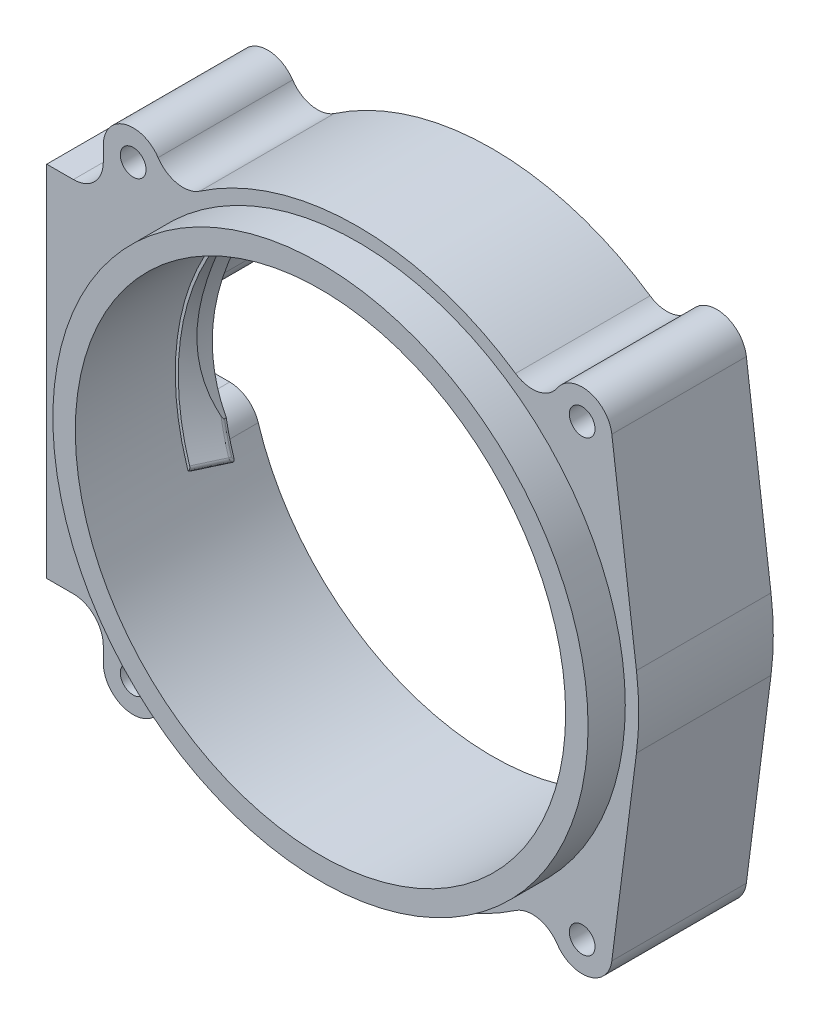
SolidWorks part; units mm, degrees
material "ABS"
ref_plane "前视基准面" through (0, 0, 0) normal (0, 0, 1) x (1, 0, 0)
ref_plane "上视基准面" through (0, 0, 0) normal (0, 1, 0) x (1, 0, 0)
ref_plane "右视基准面" through (0, 0, 0) normal (1, 0, 0) x (0, 0, -1)
sketch "草图1" plane through (0, 0, 0) normal (0, 0, 1) x (1, 0, 0)
  line L0 (0, 0) -> (50000, 0) construction
  line L1 (-52, 8.75) -> (-52, -8.75) construction
  line L2 (-52, 8.75) -> (-52, 30)
  line L3 (-52, -8.75) -> (-52, -30)
  line L4 (-52, 8.75) -> (-43.8969, 8.75)
  line L5 (-52, -8.75) -> (-43.8969, -8.75)
  line L6 (-42.54, 37.5) -> (-42.54, 35)
  line L7 (-47.54, 30) -> (-52, 30)
  line L8 (-47.54, -30) -> (-52, -30)
  line L9 (-42.54, -37.5) -> (-42.54, -35)
  line L10 (0, 0) -> (0, -50000) construction
  line L11 (42.4995, 38.1352) -> (46.6192, 5.9711)
  line L12 (42.4995, -38.1352) -> (46.6192, -5.9711)
  arc A0 (-39.1255, -12.2554) -> (-39.1255, 12.2554) centre (0, 0) ccw
  arc A1 (-40.0554, 8.75) -> (-40.0554, -8.75) centre (0, 0) ccw construction
  circle A2 centre (-37.54, 37.5) radius 2.15
  circle A3 centre (-37.54, -37.5) radius 2.15
  arc A4 (-33.3722, 40.2622) -> (-42.54, 37.5) centre (-37.54, 37.5) ccw
  arc A5 (-42.54, -37.5) -> (-33.3722, -40.2622) centre (-37.54, -37.5) ccw
  arc A6 (-26.3963, -38.8874) -> (26.3963, -38.8874) centre (0, 0) ccw
  arc A7 (-33.3722, 40.2622) -> (-26.3963, 38.8874) centre (-29.2045, 43.0244) ccw
  arc A8 (-33.3722, -40.2622) -> (-42.54, -37.5) centre (-37.54, -37.5) cw
  arc A9 (-33.3722, -40.2622) -> (-26.3963, -38.8874) centre (-29.2045, -43.0244) cw
  circle A10 centre (37.54, -37.5) radius 2.15
  circle A11 centre (37.54, 37.5) radius 2.15
  arc A12 (42.4995, 38.1352) -> (33.3722, 40.2622) centre (37.54, 37.5) ccw
  arc A13 (33.3722, -40.2622) -> (42.4995, -38.1352) centre (37.54, -37.5) ccw
  arc A14 (33.3722, 40.2622) -> (26.3963, 38.8874) centre (29.2045, 43.0244) cw
  arc A15 (33.3722, -40.2622) -> (26.3963, -38.8874) centre (29.2045, -43.0244) ccw
  arc A16 (26.3963, 38.8874) -> (-26.3963, 38.8874) centre (0, 0) ccw
  arc A17 (46.6192, -5.9711) -> (46.6192, 5.9711) centre (0, 0) ccw
  arc A18 (-47.54, -30) -> (-42.54, -35) centre (-47.54, -35) cw
  arc A19 (-42.54, 35) -> (-47.54, 30) centre (-47.54, 35) cw
  arc A20 (-43.8969, 8.75) -> (-39.1255, 12.2554) centre (-43.8969, 13.75) ccw
  arc A21 (-43.8969, -8.75) -> (-39.1255, -12.2554) centre (-43.8969, -13.75) cw
  point P8 (-52, 0)
  point P44 (-42.54, -30)
  point P47 (-42.54, 30)
  dimension "D1" = 82
  dimension "D5" = 4.3
  dimension "D6" = 75
  dimension "D8" = 10
  dimension "D9" = 94
  dimension "D10" = 5
  dimension "D11" = 10
  dimension "D12" = 5
  dimension "D13" = 5
  dimension "D14" = 5
  dimension "D15" = 5
  dimension "D2" = 17.5
  dimension "D3" = 52
  dimension "D4" = 60
  dimension "D7" = 14.46
extrude "凸台-拉伸1" add sketch "草图1" along normal blind 22.5 contours A21 L5 L3 L8 A18 L9 A5 A9 A6 A15 A13 L12 A17 L11 A12 A14 A16 A7 A4 L6 A19 L7 L2 L4 A20 A0 A10 A3 A2 A11 region at (-50.6348, 19.375, 0)
sketch "草图3" plane through (0, 0, 22.5) normal (0, 0, 1) x (1, 0, 0)
  line L0 (-52, -8.75) -> (-43.8969, -8.75) construction
  line L1 (-52, 8.75) -> (-43.8969, 8.75) construction
  line L2 (-52, -8.75) -> (-43.8969, -8.75)
  line L3 (-52, 8.75) -> (-43.8969, 8.75)
  line L4 (-52, 8.75) -> (-52, -8.75)
  arc A1 (-39.1255, -12.2554) -> (-43.8969, -8.75) centre (-43.8969, -13.75) ccw construction
  arc A2 (-43.8969, 8.75) -> (-39.1255, 12.2554) centre (-43.8969, 13.75) ccw construction
  arc A3 (-39.1255, -12.2554) -> (-43.8969, -8.75) centre (-43.8969, -13.75) ccw
  arc A4 (-43.8969, 8.75) -> (-39.1255, 12.2554) centre (-43.8969, 13.75) ccw
  arc A5 (-39.1255, 12.2554) -> (-39.1255, -12.2554) centre (0, 0) ccw
  arc A6 (-39.1255, -12.2554) -> (-39.1255, 12.2554) centre (0, 0) ccw construction
extrude "凸台-拉伸2" add sketch "草图3" against normal offset from surface (14.5 mm away) 8 up to face at (-14.5344, 0, 0)
sketch "草图4" plane through (-52, 0, 0) normal (-1, 0, 0) x (0, 0, 1)
  line L0 (0, 0) -> (-50000, 0) construction
  line L1 (22.5, 30) -> (22.5, -30) construction
  line L2 (22.5, 15) -> (8, 15)
  line L3 (22.5, 15) -> (22.5, 13.2)
  line L4 (22.5, 13.2) -> (8, 13.2)
  line L5 (8, 15) -> (8, 13.2)
  line L7 (22.5, -15) -> (8, -15)
  line L8 (22.5, -15) -> (22.5, -13.2)
  line L9 (22.5, -13.2) -> (8, -13.2)
  line L10 (8, -15) -> (8, -13.2)
  dimension "D1" = 26.4
  dimension "D2" = 14.5
  dimension "D3" = 1.8
extrude "凸台-拉伸3" add sketch "草图4" along normal blind 1.2
sketch "草图5" plane through (0, 0, 22.5) normal (0, 0, 1) x (1, 0, 0)
  circle A0 centre (0, 0) radius 44.75
  circle A1 centre (0, 0) radius 41
  dimension "D1" = 89.5
  dimension "D2" = 82
extrude "凸台-拉伸4" add sketch "草图5" along normal blind 11.22
sketch "草图6" plane through (0, 0, 8) normal (0, 0, -1) x (-1, 0, 0)
  line L0 (0, 0) -> (50000, 0) construction
  line L1 (0, 0) -> (0, -50000) construction
  line L2 (0, 0) -> (34.9842, -12.046) construction
  line L3 (34.9842, -12.046) -> (38.7663, -13.3483)
  line L4 (0, 0) -> (27.9243, 24.2742) construction
  line L5 (30.9431, 26.8984) -> (27.9243, 24.2742)
  arc A0 (34.9842, -12.046) -> (27.9243, 24.2742) centre (0, 0) ccw
  arc A1 (39.1255, 12.2554) -> (39.1255, -12.2554) centre (0, 0) ccw construction
  arc A2 (38.7663, -13.3483) -> (30.9431, 26.8984) centre (0, 0) ccw
  dimension "D1" = 37
  dimension "D2" = 19
  dimension "D3" = 41
extrude "凸台-拉伸5" add sketch "草图6" against normal blind 4
chamfer "倒角1" distance 3.5 angle 45 1 edges at (-36.3202, 7.0599, 12)
fillet "圆角1" radius 1 1 edges at (-36.6388, -12.6158, 10.25)
fillet "圆角2" radius 0.5 2 edges at (-35.1439, -11.5717, 8.3208) (-36.2234, 7.541, 8.5)
sketch "草图7" plane through (0, 0, 12) normal (0, 0, 1) x (1, 0, 0)
  line L0 (-38.7663, -13.3483) -> (-35.8361, -12.3394) construction
  line L1 (-30.9431, 26.8984) -> (-27.9243, 24.2742)
  arc A0 (-27.9243, 24.2742) -> (-35.2902, -11.1176) centre (0, 0) ccw construction
  arc A1 (-27.9243, 24.2742) -> (-36.4745, -6.2135) centre (0, 0) ccw
  spline S0 degree 3 poles (-36.4745, -6.2135) (-42.0845, 4.603) (-36.5338, 17.4065) (-30.9431, 26.8984) knots 0 0 0 0 1 1 1 1
  dimension "D1" = 6
extrude "切除-拉伸1" cut sketch "草图7" against normal blind 4
sketch "草图8" plane through (0, 0, 22.5) normal (0, 0, 1) x (1, 0, 0)
  line L1 (-53.2, 15) -> (-52, 15)
  line L2 (-53.2, 15) -> (-53.2, 13.2)
  line L3 (-53.2, 13.2) -> (-52, 13.2)
  line L4 (-52, 15) -> (-52, 13.2)
  line L5 (-53.2, -13.2) -> (-52, -13.2)
  line L6 (-53.2, -13.2) -> (-53.2, -15)
  line L7 (-53.2, -15) -> (-52, -15)
  line L8 (-52, -13.2) -> (-52, -15)
extrude "切除-拉伸2" cut sketch "草图8" against normal blind 60
sketch "草图9" plane through (0, 0, 33.72) normal (0, 0, 1) x (1, 0, 0)
  circle A0 centre (0, 0) radius 44.75 construction
  circle A1 centre (0, 0) radius 44.75
extrude "切除-拉伸3" cut sketch "草图9" against normal blind 5
